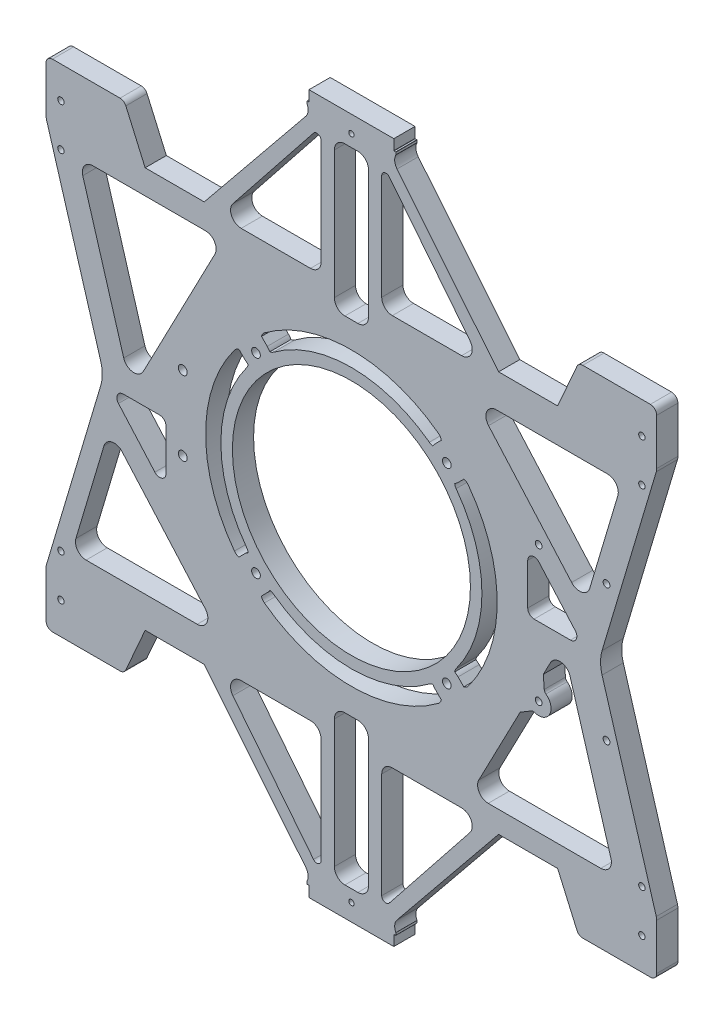
SolidWorks part; units mm, degrees
material "Thornel Mat VMA"
ref_plane "前视基准面" through (0, 0, 0) normal (0, 0, 1) x (1, 0, 0)
ref_plane "上视基准面" through (0, 0, 0) normal (0, 1, 0) x (1, 0, 0)
ref_plane "右视基准面" through (0, 0, 0) normal (1, 0, 0) x (0, 0, -1)
sketch "草图1" plane through (0, 0, 0) normal (0, 0, 1) x (1, 0, 0)
  line L0 (0, 0) -> (-45, 0) construction
  line L1 (-45, 0) -> (-45, 45) construction
  line L2 (0, 0) -> (0, 75) construction
  line L3 (0, 0) -> (75, 0) construction
  line L4 (-39.6967, 50.3033) -> (-47.4639, 58.0705)
  line L5 (-50.3033, 39.6967) -> (-58.0705, 47.4639)
  line L6 (50.3033, 39.6967) -> (58.0705, 47.4639)
  line L7 (39.6967, 50.3033) -> (47.4639, 58.0705)
  line L8 (39.6967, -50.3033) -> (47.4639, -58.0705)
  line L9 (50.3033, -39.6967) -> (58.0705, -47.4639)
  line L10 (-50.3033, -39.6967) -> (-58.0705, -47.4639)
  line L11 (-39.6967, -50.3033) -> (-47.4639, -58.0705)
  circle A0 centre (0, 0) radius 85
  circle A1 centre (0, 0) radius 75
  circle A2 centre (-45, 45) radius 2.05
  circle A3 centre (45, 45) radius 2.05
  circle A4 centre (45, -45) radius 2.05
  circle A5 centre (-45, -45) radius 2.05
  circle A6 centre (-45, 45) radius 7.5
  circle A7 centre (45, 45) radius 7.5
  circle A8 centre (45, -45) radius 7.5
  circle A9 centre (-45, -45) radius 7.5
  point P41 (0, 0)
  dimension "D1" = 170
  dimension "D2" = 10
  dimension "D5" = 4.1
  dimension "D6" = 15
  dimension "D3" = 45
  dimension "D4" = 45
  dimension "D7" = 135
  dimension "D8" = 4
extrude "凸台-拉伸1" add sketch "草图1" along normal mid plane 10 contours A0 A1 | A6 L4 A1 L5 | A6 A2 | A7 L6 A1 L7 | A7 A3 | A8 A4 | A8 L8 A1 L9 | A9 A5 | A9 L10 A1 L11 region at (-50.8703, 50.8703, 0) region at (-38.2669, 47.7889, 0) region at (50.8703, 50.8703, 0) region at (47.7889, 51.7331, 0) region at (-50.8703, -50.8703, 0) region at (-42.2111, -38.2669, 0) region at (50.8703, -50.8703, 0) region at (51.7331, -42.2111, 0) region at (-82.5958, 0, 0)
sketch "草图2" plane through (0, 0, 0) normal (0, 0, 1) x (1, 0, 0)
  line L0 (0, 0) -> (0, 165) construction
  line L1 (20, 165) -> (-20, 165)
  line L2 (-20, 165) -> (-20, 82.6136)
  line L3 (20, 165) -> (20, 82.6136)
  line L4 (0, 0) -> (-75, 0) construction
  line L5 (20, -165) -> (20, -82.6136)
  line L6 (20, -165) -> (-20, -165)
  line L7 (-20, -165) -> (-20, -82.6136)
  line L8 (97.2728, 94.4582) -> (74.7025, 94.4582)
  line L9 (-20, 160) -> (-72.3745, 95.5659)
  line L10 (-97.2728, 94.4582) -> (-74.7025, 94.4582)
  line L11 (97.2728, 94.4582) -> (125.2785, 158.2066)
  line L12 (128.0251, 160) -> (144, 160)
  line L13 (144, 160) -> (144, 92.25)
  line L14 (143.7919, 90.8225) -> (118.2235, 4.9964)
  line L15 (0, 0) -> (177.7044, 0) construction
  line L16 (20, 160) -> (72.3745, 95.5659)
  line L17 (128.0251, -160) -> (144, -160)
  line L18 (144, -160) -> (144, -92.25)
  line L19 (143.7919, -90.8225) -> (118.2235, -4.9964)
  line L20 (-97.2728, -94.4582) -> (-74.7025, -94.4582)
  line L21 (0, 0) -> (-177.7044, 0) construction
  line L22 (97.2728, -94.4582) -> (74.7025, -94.4582)
  line L23 (20, -160) -> (72.3745, -95.5659)
  line L24 (97.2728, -94.4582) -> (125.2785, -158.2066)
  line L25 (-97.2728, -94.4582) -> (-125.2785, -158.2066)
  line L26 (-143.7919, -90.8225) -> (-118.2235, -4.9964)
  line L27 (-144, -160) -> (-144, -92.25)
  line L28 (-128.0251, -160) -> (-144, -160)
  line L29 (-143.7919, 90.8225) -> (-118.2235, 4.9964)
  line L30 (-144, 160) -> (-144, 92.25)
  line L31 (-128.0251, 160) -> (-144, 160)
  line L32 (-97.2728, 94.4582) -> (-125.2785, 158.2066)
  line L33 (-20, -160) -> (-72.3745, -95.5659)
  circle A0 centre (0, 0) radius 85 construction
  circle A1 centre (0, 0) radius 85
  arc A2 (-58.0705, 47.4639) -> (-58.0705, -47.4639) centre (0, 0) ccw construction
  arc A3 (118.2235, 4.9964) -> (118.2235, -4.9964) centre (134.9951, 0) ccw
  arc A4 (128.0251, 160) -> (125.2785, 158.2066) centre (128.0251, 157) ccw
  circle A5 centre (20, 160) radius 1.5
  arc A6 (74.7025, 94.4582) -> (72.3745, 95.5659) centre (74.7025, 97.4582) cw
  arc A7 (144, 92.25) -> (143.7919, 90.8225) centre (139, 92.25) cw
  circle A8 centre (20, -160) radius 1.5
  arc A9 (128.0251, -160) -> (125.2785, -158.2066) centre (128.0251, -157) cw
  arc A10 (74.7025, -94.4582) -> (72.3745, -95.5659) centre (74.7025, -97.4582) ccw
  arc A11 (-74.7025, 94.4582) -> (-72.3745, 95.5659) centre (-74.7025, 97.4582) ccw
  arc A12 (-74.7025, -94.4582) -> (-72.3745, -95.5659) centre (-74.7025, -97.4582) cw
  arc A13 (-128.0251, -160) -> (-125.2785, -158.2066) centre (-128.0251, -157) ccw
  arc A14 (-144, 92.25) -> (-143.7919, 90.8225) centre (-139, 92.25) ccw
  arc A15 (-128.0251, 160) -> (-125.2785, 158.2066) centre (-128.0251, 157) cw
  arc A16 (-118.2235, 4.9964) -> (-118.2235, -4.9964) centre (-134.9951, 0) cw
  circle A17 centre (-20, -160) radius 1.5
  circle A18 centre (-20, 160) radius 1.5
  arc A19 (144, -92.25) -> (143.7919, -90.8225) centre (139, -92.25) ccw
  arc A20 (-144, -92.25) -> (-143.7919, -90.8225) centre (-139, -92.25) cw
  dimension "D7" = 35
  dimension "D8" = 3
  dimension "D9" = 3
  dimension "D11" = 3
  dimension "D12" = 5
  dimension "D1" = 165
  dimension "D2" = 20
  dimension "D3" = 144
  dimension "D6" = 160
  dimension "D10" = 5
extrude "凸台-拉伸2" add sketch "草图2" along normal mid plane 10 contours L18 A19 L19 A3 L14 A7 L13 L12 A4 L11 L8 A6 L16 A5 L3 A1 L5 A8 L23 A10 L22 L24 A9 L17 | A20 L27 L28 A13 L25 L20 A12 L33 A17 L7 A1 L2 A18 L9 A11 L10 L32 A15 L31 L30 A14 L29 A16 L26 | L2 A18 A1 L3 A5 L1 | A17 L7 L6 L5 A8 A1 region at (0, 124.5238, 0) region at (90.7935, 0, 0) region at (-90.7935, 0, 0) region at (0, -124.5238, 0)
sketch "草图4" plane through (0, 0, -5) normal (0, 0, -1) x (-1, 0, 0)
  line L0 (-20, 165) -> (-20, 160)
  line L1 (-20, 160) -> (-20.9461, 160)
  line L2 (-20.9461, 160) -> (-20.9461, 158.836)
  line L3 (-20.9461, 158.836) -> (-72.3745, 95.5659) construction
  line L4 (-20, 165) -> (20, 165) construction
  line L5 (-20.9461, 158.836) -> (20.9461, 158.836)
  line L6 (0, 0) -> (0, 165) construction
  line L7 (-20, 165) -> (20, 165)
  line L8 (0, 165) -> (0, 158.836)
  line L9 (20, 165) -> (20, 160)
  line L10 (20, 160) -> (20.9461, 160)
  line L11 (20.9461, 160) -> (20.9461, 158.836)
  line L12 (0, 0) -> (75, 0) construction
  line L13 (-20, -165) -> (-20, -160)
  line L14 (-20, -160) -> (-20.9461, -160)
  line L15 (-20.9461, -160) -> (-20.9461, -158.836)
  line L16 (-20.9461, -158.836) -> (20.9461, -158.836)
  line L17 (20.9461, -160) -> (20.9461, -158.836)
  line L18 (20, -160) -> (20.9461, -160)
  line L19 (20, -165) -> (20, -160)
  line L20 (-20, -165) -> (20, -165)
  line L21 (-20.9461, 158.836) -> (-20.1628, 157.9276)
  line L22 (-20.1628, 157.9276) -> (20.1628, 157.9276)
  line L23 (0, 157.9276) -> (0, 158.836)
  line L24 (20.9461, 158.836) -> (20.1628, 157.9276)
  line L25 (20.9461, -158.836) -> (20.1628, -157.9276)
  line L26 (-20.1628, -157.9276) -> (20.1628, -157.9276)
  line L27 (-20.9461, -158.836) -> (-20.1628, -157.9276)
  arc A0 (-20.9461, 158.836) -> (-20, 161.5) centre (-20, 160) ccw construction
  arc A1 (58.0705, -47.4639) -> (58.0705, 47.4639) centre (0, 0) ccw construction
  dimension "D1" = 5
extrude "凸台-拉伸6" add sketch "草图4" against normal blind 10 contours L8 L7 L0 L1 L2 L5 | L11 L10 L9 L7 L8 L5 | L22 L23 L5 L21 | L24 L5 L23 L22 | L27 L16 L25 L26 | L13 L20 L19 L18 L17 L16 L15 L14 region at (10.0927, 161.8959, -5) region at (-10.0927, 161.8959, -5) region at (10.2785, 158.3847, -5) region at (-10.2785, 158.3847, -5) region at (0, -161.8959, -5) region at (0, -158.3847, -5)
fillet "圆角2" radius 0.1 16 edges at (-20.9461, -158.836, 0) (-20.9461, -160, 0) (-20, -160, 0) (20, -160, 0) (20.9461, -158.836, 0) (20.9461, -160, 0) (144, -160, 0) (-144, -160, 0) (-144, 160, 0) (144, 160, 0) (-20.9461, 160, 0) (-20.9461, 158.836, 0) (-20, 160, 0) (20, 160, 0) (20.9461, 158.836, 0) (20.9461, 160, 0)
sketch "草图5" plane through (0, 0, -5) normal (0, 0, -1) x (-1, 0, 0)
  line L0 (-17.8628, 148.3204) -> (-55.9055, 100.4788)
  line L1 (-3.0559, 151.3528) -> (3.0559, 151.3528)
  line L2 (-8.0559, 146.3528) -> (-8.0559, 86.0484)
  line L3 (-3.0559, 81.0484) -> (3.0559, 81.0484)
  line L4 (8.0559, 146.3528) -> (8.0559, 86.0484)
  line L5 (-8.0559, 151.3528) -> (8.0559, 81.0484) construction
  line L6 (-8.0559, 81.0484) -> (8.0559, 151.3528) construction
  line L7 (-51.992, 92.3668) -> (-19.2974, 92.3668)
  line L8 (-14.2974, 147.0756) -> (-14.2974, 97.3668)
  line L9 (0, 116.2006) -> (0, 165) construction
  line L10 (-20, 165) -> (20, 165) construction
  line L11 (17.8628, 148.3204) -> (55.9055, 100.4788)
  line L12 (51.992, 92.3668) -> (19.2974, 92.3668)
  line L13 (14.2974, 147.0756) -> (14.2974, 97.3668)
  line L14 (-88.412, 26.3046) -> (-105.5842, 6.8255)
  line L15 (-103.3338, 1.8417) -> (-86.1616, 1.8417)
  line L16 (-83.1616, 4.8417) -> (-83.1616, 24.3207)
  line L17 (125.1487, -79.7032) -> (72.7148, -79.7032)
  line L18 (108.1546, -26.9417) -> (68.9642, -71.3967)
  line L19 (129.9406, -73.2756) -> (116.6971, -28.8206)
  line L20 (92.6888, -27.5787) -> (109.8611, -8.0997)
  line L21 (107.6107, -3.1158) -> (90.4384, -3.1158)
  line L22 (87.4384, -6.1158) -> (87.4384, -25.5948)
  line L23 (64.3546, 75.6522) -> (98.1568, 10.8094)
  line L24 (107.3824, 11.6932) -> (126.6997, 76.536)
  line L25 (121.9078, 82.9635) -> (68.7883, 82.9635)
  line L26 (0, 0) -> (75, 0) construction
  line L27 (14.2974, -147.0756) -> (14.2974, -97.3668)
  line L28 (51.992, -92.3668) -> (19.2974, -92.3668)
  line L29 (17.8628, -148.3204) -> (55.9055, -100.4788)
  line L30 (-3.0559, -81.0484) -> (3.0559, -81.0484)
  line L31 (8.0559, -146.3528) -> (8.0559, -86.0484)
  line L32 (-3.0559, -151.3528) -> (3.0559, -151.3528)
  line L33 (-8.0559, -146.3528) -> (-8.0559, -86.0484)
  line L34 (-17.8628, -148.3204) -> (-55.9055, -100.4788)
  line L36 (-125.6638, 72.0015) -> (-112.4202, 27.5465)
  line L37 (-103.8777, 25.6676) -> (-64.6873, 70.1226)
  line L38 (-143.7919, 90.8225) -> (-118.2235, 4.9964) construction
  line L40 (-120.8719, 78.429) -> (-68.4379, 78.429)
  line L41 (-103.1056, -12.9673) -> (-122.4228, -77.8101)
  line L42 (-117.6309, -84.2376) -> (-64.5114, -84.2376)
  line L43 (-60.0777, -76.9263) -> (-93.88, -12.0835)
  line L44 (-143.7919, -90.8225) -> (-118.2235, -4.9964) construction
  line L45 (-51.992, -92.3668) -> (-19.2974, -92.3668)
  line L46 (-14.2974, -147.0756) -> (-14.2974, -97.3668)
  arc A0 (3.0559, 81.0484) -> (8.0559, 86.0484) centre (3.0559, 86.0484) ccw
  arc A1 (-3.0559, 81.0484) -> (-8.0559, 86.0484) centre (-3.0559, 86.0484) cw
  arc A2 (8.0559, 146.3528) -> (3.0559, 151.3528) centre (3.0559, 146.3528) ccw
  arc A3 (-3.0559, 151.3528) -> (-8.0559, 146.3528) centre (-3.0559, 146.3528) ccw
  arc A4 (-14.2974, 147.0756) -> (-17.8628, 148.3204) centre (-16.2974, 147.0756) ccw
  arc A5 (-19.2974, 92.3668) -> (-14.2974, 97.3668) centre (-19.2974, 97.3668) ccw
  arc A6 (-51.992, 92.3668) -> (-55.9055, 100.4788) centre (-51.992, 97.3668) cw
  arc A7 (51.992, 92.3668) -> (55.9055, 100.4788) centre (51.992, 97.3668) ccw
  arc A8 (14.2974, 147.0756) -> (17.8628, 148.3204) centre (16.2974, 147.0756) cw
  arc A9 (19.2974, 92.3668) -> (14.2974, 97.3668) centre (19.2974, 97.3668) cw
  arc A11 (-83.1616, 24.3207) -> (-88.412, 26.3046) centre (-86.1616, 24.3207) ccw
  arc A12 (-83.1616, 4.8417) -> (-86.1616, 1.8417) centre (-86.1616, 4.8417) cw
  arc A13 (-103.3338, 1.8417) -> (-105.5842, 6.8255) centre (-103.3338, 4.8417) cw
  arc A14 (125.1487, -79.7032) -> (129.9406, -73.2756) centre (125.1487, -74.7032) ccw
  arc A15 (-64.5114, -84.2376) -> (-60.0777, -76.9263) centre (-64.5114, -79.2376) ccw
  arc A16 (-117.6309, -84.2376) -> (-122.4228, -77.8101) centre (-117.6309, -79.2376) cw
  arc A17 (-93.88, -12.0835) -> (-103.1056, -12.9673) centre (-98.3137, -14.3948) ccw
  arc A18 (-103.8777, 25.6676) -> (-112.4202, 27.5465) centre (-107.6283, 28.9741) cw
  arc A19 (-68.4379, 78.429) -> (-64.6873, 70.1226) centre (-68.4379, 73.429) cw
  arc A20 (-120.8719, 78.429) -> (-125.6638, 72.0015) centre (-120.8719, 73.429) ccw
  arc A21 (72.7148, -79.7032) -> (68.9642, -71.3967) centre (72.7148, -74.7032) cw
  arc A22 (108.1546, -26.9417) -> (116.6971, -28.8206) centre (111.9052, -30.2482) cw
  arc A23 (107.6107, -3.1158) -> (109.8611, -8.0997) centre (107.6107, -6.1158) cw
  arc A24 (87.4384, -25.5948) -> (92.6888, -27.5787) centre (90.4384, -25.5948) ccw
  arc A25 (87.4384, -6.1158) -> (90.4384, -3.1158) centre (90.4384, -6.1158) cw
  arc A26 (98.1568, 10.8094) -> (107.3824, 11.6932) centre (102.5905, 13.1207) ccw
  arc A27 (68.7883, 82.9635) -> (64.3546, 75.6522) centre (68.7883, 77.9635) ccw
  arc A28 (121.9078, 82.9635) -> (126.6997, 76.536) centre (121.9078, 77.9635) cw
  arc A29 (58.0705, -47.4639) -> (58.0705, 47.4639) centre (0, 0) ccw construction
  arc A30 (14.2974, -147.0756) -> (17.8628, -148.3204) centre (16.2974, -147.0756) ccw
  arc A31 (19.2974, -92.3668) -> (14.2974, -97.3668) centre (19.2974, -97.3668) ccw
  arc A32 (51.992, -92.3668) -> (55.9055, -100.4788) centre (51.992, -97.3668) cw
  arc A33 (3.0559, -81.0484) -> (8.0559, -86.0484) centre (3.0559, -86.0484) cw
  arc A34 (8.0559, -146.3528) -> (3.0559, -151.3528) centre (3.0559, -146.3528) cw
  arc A35 (-3.0559, -81.0484) -> (-8.0559, -86.0484) centre (-3.0559, -86.0484) ccw
  arc A36 (-3.0559, -151.3528) -> (-8.0559, -146.3528) centre (-3.0559, -146.3528) cw
  arc A37 (-51.992, -92.3668) -> (-55.9055, -100.4788) centre (-51.992, -97.3668) ccw
  arc A38 (-14.2974, -147.0756) -> (-17.8628, -148.3204) centre (-16.2974, -147.0756) cw
  arc A39 (-19.2974, -92.3668) -> (-14.2974, -97.3668) centre (-19.2974, -97.3668) cw
  point P103 (2.1384, -0.6371)
  dimension "D1" = 5
  dimension "D2" = 2
  dimension "D3" = 5
  dimension "D5" = 5
  dimension "D7" = 3
  dimension "D4" = 12
  dimension "D8" = 2
extrude "切除-拉伸3" cut sketch "草图5" against normal blind 10
sketch "草图6" plane through (0, 0, -5) normal (0, 0, -1) x (-1, 0, 0)
  line L0 (-144, 159.9) -> (-144, 92.25) construction
  line L1 (144, -116.9859) -> (-144, -116.9859)
  line L2 (144, -116.9859) -> (144, 116.9859)
  line L3 (144, 116.9859) -> (-144, 116.9859)
  line L4 (-144, -116.9859) -> (-144, 116.9859)
  line L5 (144, -116.9859) -> (-144, 116.9859) construction
  line L6 (144, 116.9859) -> (-144, -116.9859) construction
  line L7 (-144, 116.9859) -> (-144, 164.0031)
  line L8 (-144, 164.0031) -> (-92.698, 164.0031)
  line L9 (-92.698, 164.0031) -> (-92.698, 116.9859)
  line L10 (144, 116.9859) -> (159.694, 195.8915)
  line L11 (159.694, 195.8915) -> (92.9548, 181.2005)
  line L12 (92.9548, 181.2005) -> (88.7574, 116.9859)
  line L13 (144, -116.9859) -> (155.4979, -186.4371)
  line L14 (155.4979, -186.4371) -> (58.8401, -186.4371)
  line L15 (58.8401, -186.4371) -> (88.7574, -116.9859)
  line L16 (-78.9592, -116.9859) -> (-111.1785, -202.2989)
  line L17 (-111.1785, -202.2989) -> (-230.5289, -157.2251)
  line L18 (-230.5289, -157.2251) -> (-144, -116.9859)
  point P0 (0, 0)
extrude "切除-拉伸5" cut sketch "草图6" against normal blind 10 contours L9 L8 L7 L3 | L11 L12 L3 L10 | L18 L17 L16 L1 | L15 L14 L13 L1 region at (-111.3553, -154.8675, -5) region at (-122.4434, 153.8219, -5) region at (142.2314, -153.6143, -5) region at (118.349, 140.4945, -5)
fillet "圆角3" radius 3 8 edges at (-144, -116.9859, 0) (-107.1696, -116.9859, 0) (107.1696, -116.9859, 0) (144, -116.9859, 0) (-144, 116.9859, 0) (-107.1696, 116.9859, 0) (107.1696, 116.9859, 0) (144, 116.9859, 0)
ref_plane "基准面1" through (0, 0, 0) normal (1, 0, 0) x (0, 0, -1)
ref_plane "基准面2" through (0, 0, 0) normal (0, 1, 0) x (1, 0, 0)
sketch "草图7" plane through (0, 0, -5) normal (0, 0, -1) x (-1, 0, 0)
  circle A0 centre (-137, 101.9859) radius 1.5 construction
  circle A1 centre (-137, 81.9859) radius 1.5 construction
  circle A2 centre (-137, 101.9859) radius 1.5
  circle A3 centre (-137, 81.9859) radius 1.5
extrude "切除-拉伸6" cut sketch "草图7" against normal blind 10
mirror "镜向1" about plane through (0, 0, 0) normal (1, 0, 0) of "切除-拉伸6"
mirror "镜向2" about plane through (0, 0, 0) normal (0, 1, 0) of "镜向1", "切除-拉伸6"
sketch "草图8" plane through (0, 0, -5) normal (0, 0, -1) x (-1, 0, 0)
  circle A0 centre (0, 157) radius 1.25 construction
  circle A1 centre (0, 157) radius 1.25
extrude "切除-拉伸7" cut sketch "草图8" against normal blind 10
mirror "镜向3" about plane through (0, 0, 0) normal (0, 1, 0) of "切除-拉伸7"
sketch "草图14" plane through (0, 0, -5) normal (0, 0, -1) x (-1, 0, 0)
  line L0 (-74.7025, 94.4582) -> (-69.4089, 94.4582)
  line L1 (-69.4089, 94.4582) -> (-17.1025, 158.8085)
  line L2 (-17.1025, 158.8085) -> (-20.9685, 158.8085)
  line L3 (-20.9685, 158.8085) -> (-72.3745, 95.5659) construction
  line L4 (-74.7025, 94.4582) -> (-20.9685, 158.8085)
  line L5 (0, 55) -> (0, -55) construction
  line L6 (74.7025, 94.4582) -> (69.4089, 94.4582)
  line L7 (69.4089, 94.4582) -> (17.1025, 158.8085)
  line L8 (17.1025, 158.8085) -> (20.9685, 158.8085)
  line L9 (74.7025, 94.4582) -> (20.9685, 158.8085)
  line L10 (55, 0) -> (-55, 0) construction
  line L11 (74.7025, -94.4582) -> (20.9685, -158.8085)
  line L12 (17.1025, -158.8085) -> (20.9685, -158.8085)
  line L13 (69.4089, -94.4582) -> (17.1025, -158.8085)
  line L14 (74.7025, -94.4582) -> (69.4089, -94.4582)
  line L15 (-74.7025, -94.4582) -> (-69.4089, -94.4582)
  line L16 (-69.4089, -94.4582) -> (-17.1025, -158.8085)
  line L17 (-17.1025, -158.8085) -> (-20.9685, -158.8085)
  line L18 (-74.7025, -94.4582) -> (-20.9685, -158.8085)
  dimension "D1" = 3
extrude "切除-拉伸11" cut sketch "草图14" against normal blind 10
fillet "圆角6" radius 5 2 edges at (-17.1025, 158.8085, 0) (17.1025, 158.8085, 0)
fillet "圆角7" radius 5 2 edges at (-17.1025, -158.8085, 0) (17.1025, -158.8085, 0)
sketch "草图16" plane through (0, 0, -5) normal (0, 0, -1) x (-1, 0, 0)
  circle A0 centre (79.5324, 20.6951) radius 2.1 construction
  circle A1 centre (79.5324, -14.3049) radius 2.1 construction
  circle A2 centre (79.5324, 20.6951) radius 2.1
  circle A3 centre (79.5324, -14.3049) radius 2.1
extrude "切除-拉伸12" cut sketch "草图16" against normal blind 10
sketch "草图17" plane through (0, 0, -5) normal (0, 0, -1) x (-1, 0, 0)
  line L0 (0, 0) -> (0, 65.1632) construction
  circle A0 centre (0, 0) radius 56.1396
  circle A1 centre (0, 0) radius 75
  arc A2 (39.6967, 50.3033) -> (50.3033, 39.6967) centre (45, 45) ccw construction
  arc A3 (-38.8982, 52.2798) -> (38.8982, 52.2798) centre (0, 0) cw construction
  arc A4 (41.0441, 55.1639) -> (-41.0441, 55.1639) centre (0, 0) ccw
  arc A5 (36.7523, 49.3956) -> (-36.7523, 49.3956) centre (0, 0) ccw
  arc A6 (36.7523, 49.3956) -> (41.0441, 55.1639) centre (38.8982, 52.2798) ccw
  arc A7 (-41.0441, 55.1639) -> (-36.7523, 49.3956) centre (-38.8982, 52.2798) ccw
  arc A8 (49.3956, -36.7523) -> (49.3956, 36.7523) centre (0, 0) ccw
  arc A9 (49.3956, -36.7523) -> (55.1639, -41.0441) centre (52.2798, -38.8982) ccw
  arc A10 (55.1639, 41.0441) -> (49.3956, 36.7523) centre (52.2798, 38.8982) ccw
  arc A11 (55.1639, -41.0441) -> (55.1639, 41.0441) centre (0, 0) ccw
  arc A12 (52.2798, 38.8982) -> (52.2798, -38.8982) centre (0, 0) cw construction
  arc A13 (-36.7523, -49.3956) -> (36.7523, -49.3956) centre (0, 0) ccw
  arc A14 (-36.7523, -49.3956) -> (-41.0441, -55.1639) centre (-38.8982, -52.2798) ccw
  arc A15 (41.0441, -55.1639) -> (36.7523, -49.3956) centre (38.8982, -52.2798) ccw
  arc A16 (-41.0441, -55.1639) -> (41.0441, -55.1639) centre (0, 0) ccw
  arc A17 (38.8982, -52.2798) -> (-38.8982, -52.2798) centre (0, 0) cw construction
  arc A18 (-49.3956, 36.7523) -> (-49.3956, -36.7523) centre (0, 0) ccw
  arc A19 (-49.3956, 36.7523) -> (-55.1639, 41.0441) centre (-52.2798, 38.8982) ccw
  arc A20 (-55.1639, -41.0441) -> (-49.3956, -36.7523) centre (-52.2798, -38.8982) ccw
  arc A21 (-55.1639, 41.0441) -> (-55.1639, -41.0441) centre (0, 0) ccw
  arc A22 (-52.2798, -38.8982) -> (-52.2798, 38.8982) centre (0, 0) cw construction
  circle A23 centre (45, -45) radius 2.05 construction
  circle A24 centre (-45, -45) radius 2.05 construction
  circle A25 centre (45, 45) radius 2.05 construction
  circle A26 centre (-45, 45) radius 2.05 construction
  circle A27 centre (45, -45) radius 2.05
  circle A28 centre (-45, -45) radius 2.05
  circle A29 centre (45, 45) radius 2.05
  circle A30 centre (-45, 45) radius 2.05
  point P10 (0, 65.1632)
  point P22 (65.1632, 0)
  point P29 (0, -65.1632)
  point P36 (-65.1632, 0)
  point P41 (0, 0)
  dimension "D1" = 4
extrude "凸台-拉伸7" add sketch "草图17" against normal up to surface (10 mm away) up to face at (-81.6324, 20.6951, 5)
sketch "草图18" plane through (0, 0, -5) normal (0, 0, -1) x (-1, 0, 0)
  line L0 (-88.3213, -36.5191) -> (-81.1418, -36.5191)
  line L1 (-60.0777, -76.9263) -> (-93.88, -12.0835) construction
  line L81 (-117.9213, -41.1841) -> (-117.9213, -36.6841)
  line L82 (-117.9213, -36.6841) -> (-110.4213, -36.6841)
  line L83 (-110.4213, -36.6841) -> (-110.4213, -27.0841)
  line L84 (-110.4213, -27.0841) -> (-97.2213, -27.0841)
  line L85 (-97.2213, -27.0841) -> (-97.2213, -37.0841)
  line L86 (-97.2213, -37.0841) -> (-90.7213, -37.0841)
  line L87 (-90.7213, -37.0841) -> (-90.7213, -41.1841)
  line L88 (-90.7213, -41.1841) -> (-85.6213, -41.1841)
  line L89 (-85.6213, -41.1841) -> (-85.6213, -35.6841)
  line L90 (-85.6213, -35.6841) -> (-75.3213, -35.6841)
  line L91 (-75.3213, -35.6841) -> (-75.3213, -33.2841)
  line L92 (-75.3213, -33.2841) -> (-79.8213, -33.2841)
  line L93 (-79.8213, -33.2841) -> (-79.8213, -27.2841)
  line L94 (-79.8213, -27.2841) -> (-75.3213, -27.2841)
  line L95 (-75.3213, -27.2841) -> (-75.3213, -25.2841)
  line L96 (-75.3213, -25.2841) -> (-80.8213, -25.2841)
  line L97 (-80.8213, -25.2841) -> (-80.8213, -14.8841)
  line L98 (-80.8213, -14.8841) -> (-75.3213, -14.8841)
  line L99 (-75.3213, -14.8841) -> (-75.3213, -12.2841)
  line L100 (-75.3213, -12.2841) -> (-79.8213, -12.2841)
  line L101 (-79.8213, -12.2841) -> (-79.8213, -6.2841)
  line L102 (-79.8213, -6.2841) -> (-75.3213, -6.2841)
  line L103 (-75.3213, -6.2841) -> (-75.3213, -4.2841)
  line L104 (-75.3213, -4.2841) -> (-79.8213, -4.2841)
  line L105 (-79.8213, -4.2841) -> (-79.8213, 4.2159)
  line L106 (-79.8213, 4.2159) -> (-75.3213, 4.2159)
  line L107 (-75.3213, 4.2159) -> (-75.3213, 5.9492)
  line L108 (-75.3213, 5.9492) -> (-79.8213, 5.9492)
  line L109 (-79.8213, 5.9492) -> (-79.8213, 14.4492)
  line L110 (-79.8213, 14.4492) -> (-75.3213, 14.4492)
  line L111 (-75.3213, 14.4492) -> (-75.3213, 16.1826)
  line L112 (-75.3213, 16.1826) -> (-79.8213, 16.1826)
  line L113 (-79.8213, 16.1826) -> (-79.8213, 24.6826)
  line L114 (-79.8213, 24.6826) -> (-75.3213, 24.6826)
  line L115 (-75.3213, 24.6826) -> (-75.3213, 26.4159)
  line L116 (-75.3213, 26.4159) -> (-79.8213, 26.4159)
  line L117 (-79.8213, 26.4159) -> (-79.8213, 39.7159)
  line L118 (-79.8213, 39.7159) -> (-91.4713, 39.7159)
  line L119 (-91.4713, 39.7159) -> (-91.4713, 36.1159)
  line L120 (-91.4713, 36.1159) -> (-88.3213, 36.1159)
  line L121 (-90.7461, 34.7159) -> (-99.1713, 34.7159)
  line L122 (-99.1713, 34.7159) -> (-99.1713, 39.7159)
  line L123 (-99.1713, 39.7159) -> (-112.4213, 39.7159)
  line L124 (-112.4213, 39.7159) -> (-112.4213, 43.8159)
  line L125 (-112.4213, 43.8159) -> (-114.4713, 43.8159)
  line L126 (-114.4713, 43.8159) -> (-114.4713, 39.2159)
  line L127 (-114.4713, 39.2159) -> (-122.1713, 39.2159)
  line L128 (-122.1713, 39.2159) -> (-122.1713, 43.8159)
  line L129 (-122.1713, 43.8159) -> (-124.4213, 43.8159)
  line L130 (-124.4213, 43.8159) -> (-124.4213, 38.7159)
  line L131 (-124.4213, 38.7159) -> (-128.8213, 38.7159)
  line L132 (-128.8213, 38.7159) -> (-128.8213, 26.4159)
  line L133 (-128.8213, 26.4159) -> (-133.3213, 26.4159)
  line L134 (-133.3213, 26.4159) -> (-133.3213, 24.6826)
  line L135 (-133.3213, 24.6826) -> (-128.8213, 24.6826)
  line L136 (-128.8213, 24.6826) -> (-128.8213, 16.1826)
  line L137 (-128.8213, 16.1826) -> (-133.3213, 16.1826)
  line L138 (-133.3213, 16.1826) -> (-133.3213, 14.4492)
  line L139 (-133.3213, 14.4492) -> (-128.8213, 14.4492)
  line L140 (-128.8213, 14.4492) -> (-128.8213, 5.9492)
  line L141 (-128.8213, 5.9492) -> (-133.3213, 5.9492)
  line L142 (-133.3213, 5.9492) -> (-133.3213, 4.2159)
  line L143 (-133.3213, 4.2159) -> (-128.8213, 4.2159)
  line L144 (-128.8213, 4.2159) -> (-128.8213, -4.2841)
  line L145 (-128.8213, -4.2841) -> (-133.3213, -4.2841)
  line L146 (-133.3213, -4.2841) -> (-133.3213, -6.2841)
  line L147 (-133.3213, -6.2841) -> (-128.8213, -6.2841)
  line L148 (-128.8213, -6.2841) -> (-128.8213, -12.2841)
  line L149 (-128.8213, -12.2841) -> (-133.3213, -12.2841)
  line L150 (-133.3213, -12.2841) -> (-133.3213, -14.3841)
  line L151 (-133.3213, -14.3841) -> (-127.8213, -14.3841)
  line L152 (-127.8213, -14.3841) -> (-127.8213, -24.7841)
  line L153 (-127.8213, -24.7841) -> (-133.3213, -24.7841)
  line L154 (-133.3213, -24.7841) -> (-133.3213, -27.2841)
  line L155 (-133.3213, -27.2841) -> (-128.8213, -27.2841)
  line L156 (-128.8213, -27.2841) -> (-128.8213, -33.2841)
  line L157 (-128.8213, -33.2841) -> (-133.3213, -33.2841)
  line L158 (-133.3213, -33.2841) -> (-133.3213, -35.6841)
  line L159 (-133.3213, -35.6841) -> (-123.0213, -35.6841)
  line L160 (-123.0213, -35.6841) -> (-123.0213, -41.1841)
  line L161 (-123.0213, -41.1841) -> (-117.9213, -41.1841)
  line L162 (-117.9213, -41.1841) -> (-117.9213, -36.6841)
  line L163 (-117.9213, -36.6841) -> (-110.4213, -36.6841)
  line L164 (-110.4213, -36.6841) -> (-110.4213, -27.0841)
  line L165 (-110.4213, -27.0841) -> (-97.2213, -27.0841)
  line L166 (-97.2213, -27.0841) -> (-97.2213, -37.0841)
  line L167 (-97.2213, -37.0841) -> (-90.7213, -37.0841)
  line L168 (-90.7213, -37.0841) -> (-90.7213, -41.1841)
  line L169 (-90.7213, -41.1841) -> (-85.6213, -41.1841)
  line L170 (-85.6213, -41.1841) -> (-85.6213, -35.6841)
  line L171 (-85.6213, -35.6841) -> (-75.3213, -35.6841)
  line L172 (-75.3213, -35.6841) -> (-75.3213, -33.2841)
  line L173 (-75.3213, -33.2841) -> (-79.8213, -33.2841)
  line L174 (-79.8213, -33.2841) -> (-79.8213, -27.2841)
  line L175 (-79.8213, -27.2841) -> (-75.3213, -27.2841)
  line L176 (-75.3213, -27.2841) -> (-75.3213, -25.2841)
  line L177 (-75.3213, -25.2841) -> (-80.8213, -25.2841)
  line L178 (-80.8213, -25.2841) -> (-80.8213, -14.8841)
  line L179 (-80.8213, -14.8841) -> (-75.3213, -14.8841)
  line L180 (-75.3213, -14.8841) -> (-75.3213, -12.2841)
  line L181 (-75.3213, -12.2841) -> (-79.8213, -12.2841)
  line L182 (-79.8213, -12.2841) -> (-79.8213, -6.2841)
  line L183 (-79.8213, -6.2841) -> (-75.3213, -6.2841)
  line L184 (-75.3213, -6.2841) -> (-75.3213, -4.2841)
  line L185 (-75.3213, -4.2841) -> (-79.8213, -4.2841)
  line L186 (-79.8213, -4.2841) -> (-79.8213, 4.2159)
  line L187 (-79.8213, 4.2159) -> (-75.3213, 4.2159)
  line L188 (-75.3213, 4.2159) -> (-75.3213, 5.9492)
  line L189 (-75.3213, 5.9492) -> (-79.8213, 5.9492)
  line L190 (-79.8213, 5.9492) -> (-79.8213, 14.4492)
  line L191 (-79.8213, 14.4492) -> (-75.3213, 14.4492)
  line L192 (-75.3213, 14.4492) -> (-75.3213, 16.1826)
  line L193 (-75.3213, 16.1826) -> (-79.8213, 16.1826)
  line L194 (-79.8213, 16.1826) -> (-79.8213, 24.6826)
  line L195 (-79.8213, 24.6826) -> (-75.3213, 24.6826)
  line L196 (-75.3213, 24.6826) -> (-75.3213, 26.4159)
  line L197 (-75.3213, 26.4159) -> (-79.8213, 26.4159)
  line L198 (-79.8213, 26.4159) -> (-79.8213, 39.7159)
  line L199 (-79.8213, 39.7159) -> (-91.4713, 39.7159)
  line L200 (-91.4713, 39.7159) -> (-91.4713, 36.1159)
  line L201 (-91.4713, 36.1159) -> (-88.3213, 36.1159)
  line L202 (-90.7461, 34.7159) -> (-99.1713, 34.7159)
  line L203 (-99.1713, 34.7159) -> (-99.1713, 39.7159)
  line L204 (-99.1713, 39.7159) -> (-112.4213, 39.7159)
  line L205 (-112.4213, 39.7159) -> (-112.4213, 43.8159)
  line L206 (-112.4213, 43.8159) -> (-114.4713, 43.8159)
  line L207 (-114.4713, 43.8159) -> (-114.4713, 39.2159)
  line L208 (-114.4713, 39.2159) -> (-122.1713, 39.2159)
  line L209 (-122.1713, 39.2159) -> (-122.1713, 43.8159)
  line L210 (-122.1713, 43.8159) -> (-124.4213, 43.8159)
  line L211 (-124.4213, 43.8159) -> (-124.4213, 38.7159)
  line L212 (-124.4213, 38.7159) -> (-128.8213, 38.7159)
  line L213 (-128.8213, 38.7159) -> (-128.8213, 26.4159)
  line L214 (-128.8213, 26.4159) -> (-133.3213, 26.4159)
  line L215 (-133.3213, 26.4159) -> (-133.3213, 24.6826)
  line L216 (-133.3213, 24.6826) -> (-128.8213, 24.6826)
  line L217 (-128.8213, 24.6826) -> (-128.8213, 16.1826)
  line L218 (-128.8213, 16.1826) -> (-133.3213, 16.1826)
  line L219 (-133.3213, 16.1826) -> (-133.3213, 14.4492)
  line L220 (-133.3213, 14.4492) -> (-128.8213, 14.4492)
  line L221 (-128.8213, 14.4492) -> (-128.8213, 5.9492)
  line L222 (-128.8213, 5.9492) -> (-133.3213, 5.9492)
  line L223 (-133.3213, 5.9492) -> (-133.3213, 4.2159)
  line L224 (-133.3213, 4.2159) -> (-128.8213, 4.2159)
  line L225 (-128.8213, 4.2159) -> (-128.8213, -4.2841)
  line L226 (-128.8213, -4.2841) -> (-133.3213, -4.2841)
  line L227 (-133.3213, -4.2841) -> (-133.3213, -6.2841)
  line L228 (-133.3213, -6.2841) -> (-128.8213, -6.2841)
  line L229 (-128.8213, -6.2841) -> (-128.8213, -12.2841)
  line L230 (-128.8213, -12.2841) -> (-133.3213, -12.2841)
  line L231 (-133.3213, -12.2841) -> (-133.3213, -14.3841)
  line L232 (-133.3213, -14.3841) -> (-127.8213, -14.3841)
  line L233 (-127.8213, -14.3841) -> (-127.8213, -24.7841)
  line L234 (-127.8213, -24.7841) -> (-133.3213, -24.7841)
  line L235 (-133.3213, -24.7841) -> (-133.3213, -27.2841)
  line L236 (-133.3213, -27.2841) -> (-128.8213, -27.2841)
  line L237 (-128.8213, -27.2841) -> (-128.8213, -33.2841)
  line L238 (-128.8213, -33.2841) -> (-133.3213, -33.2841)
  line L239 (-133.3213, -33.2841) -> (-133.3213, -35.6841)
  line L240 (-133.3213, -35.6841) -> (-123.0213, -35.6841)
  line L241 (-123.0213, -35.6841) -> (-123.0213, -41.1841)
  line L242 (-123.0213, -41.1841) -> (-117.9213, -41.1841)
  circle A0 centre (-88.3213, -30.6841) radius 1.6 construction
  arc A1 (-90.7461, 34.7159) -> (-88.3213, 36.1159) centre (-88.3213, 33.3159) ccw
  arc A2 (-90.7461, 34.7159) -> (-88.3213, 36.1159) centre (-88.3213, 33.3159) ccw
  circle A3 centre (-120.3213, -30.6841) radius 1.6 construction
  circle A4 centre (-120.3213, 33.3159) radius 1.6 construction
  circle A5 centre (-88.3213, 33.3159) radius 1.6 construction
  circle A6 centre (-88.3213, -30.6841) radius 1.6
  circle A7 centre (-120.3213, -30.6841) radius 1.6
  circle A8 centre (-120.3213, 33.3159) radius 1.6
  circle A9 centre (-88.3213, 33.3159) radius 1.6
  circle A10 centre (-88.3213, -30.6841) radius 5.835
  dimension "D1" = 0
extrude "切除-拉伸13" cut sketch "草图18" against normal blind 10 contours A8 | A9 | A7 region at (120.3213, -30.6841, -5) region at (120.3213, 33.3159, -5) region at (88.3213, 33.3159, -5)
extrude "凸台-拉伸8" add sketch "草图18<3>" against normal up to surface (10 mm away) contours A10 L170 L171 A6 region at (92.3305, -26.6748, -5) up to face at (118.7213, -30.6841, 5)
sketch "草图18<3>" plane through (0, 0, -5) normal (0, 0, -1) x (-1, 0, 0) same geometry as "草图18"
sketch "草图19" plane through (0, 0, -5) normal (0, 0, -1) x (-1, 0, 0)
  line L0 (-91.0185, -25.51) -> (-90.5225, -18.5242)
  line L1 (-87.165, -24.9648) -> (-93.88, -12.0835) construction
  line L2 (-90.5225, -18.5242) -> (-79.613, -39.4519)
  line L3 (-60.0777, -76.9263) -> (-82.9704, -33.0112) construction
  line L4 (-88.3213, -30.6841) -> (-85.0677, -28.988) construction
  line L5 (-91.0185, -25.51) -> (-88.3213, -30.6841) construction
  line L6 (-85.624, -35.8582) -> (-88.3213, -30.6841) construction
  line L7 (-85.624, -35.8582) -> (-79.613, -39.4519)
  line L8 (-85.624, -35.8582) -> (-85.0677, -28.988)
  line L9 (-85.0677, -28.988) -> (-91.0185, -25.51)
  arc A0 (-87.165, -24.9648) -> (-85.6213, -35.8568) centre (-88.3213, -30.6841) ccw construction
extrude "凸台-拉伸9" add sketch "草图19" against normal up to surface (10 mm away) contours L9 L2 L0 | L8 L7 L2 region at (83.4349, -34.7661, -5) region at (88.8696, -24.3407, -5) up to face at (90.5153, -46.7347, 5)
fillet "圆角8" radius 2 2 edges at (85.624, -35.8582, 0) (91.0185, -25.51, 0)
